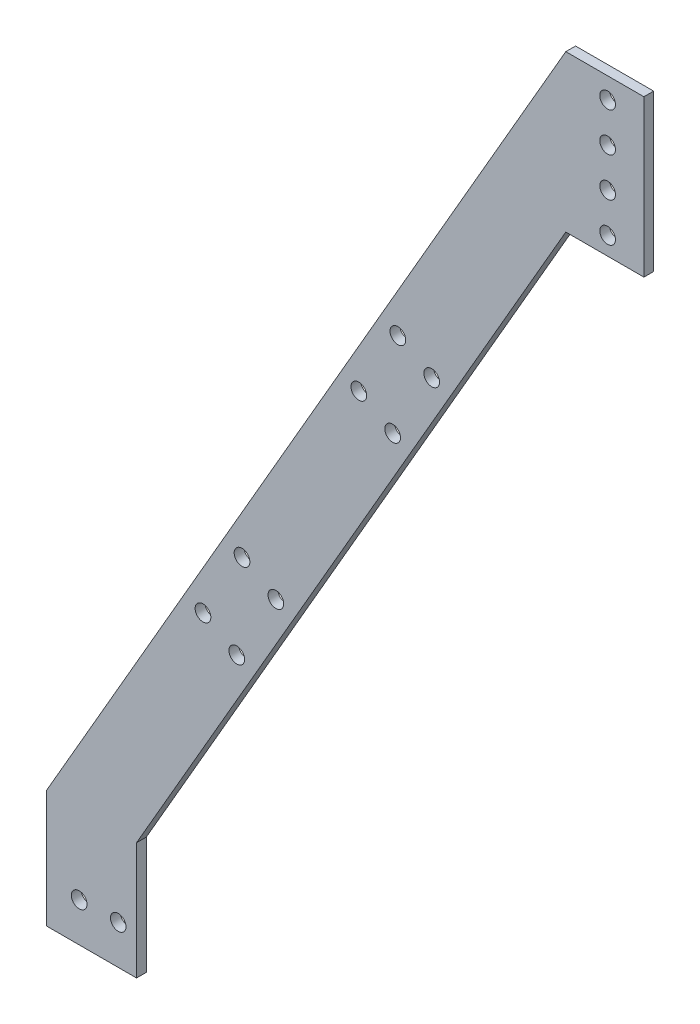
SolidWorks part; units mm, degrees
material "6061-T6 (SS)"
ref_plane "Front Plane" through (0, 0, 0) normal (0, 0, 1) x (1, 0, 0)
ref_plane "Top Plane" through (0, 0, 0) normal (0, 1, 0) x (1, 0, 0)
ref_plane "Right Plane" through (0, 0, 0) normal (1, 0, 0) x (0, 0, -1)
sketch "Sketch1" plane through (0, 0, 0) normal (0, 0, 1) x (1, 0, 0)
  line L0 (0, 0) -> (0, 38.1)
  line L1 (0, 38.1) -> (168.91, 330.6607)
  line L2 (168.91, 330.6607) -> (194.31, 330.6607)
  line L3 (194.31, 330.6607) -> (194.31, 279.8607)
  line L4 (194.31, 279.8607) -> (168.91, 279.8607)
  line L5 (168.91, 279.8607) -> (29.3294, 38.1)
  line L6 (29.3294, 38.1) -> (29.3294, 0)
  line L7 (29.3294, 0) -> (0, 0)
  dimension "D1" = 25.4
  dimension "D2" = 150
  dimension "D3" = 25.4
  dimension "D4" = 25.4
  dimension "D5" = 38.1
  dimension "D6" = 38.1
  dimension "D7" = 337.82
extrude "Boss-Extrude1" add sketch "Sketch1" along normal blind 3.175
sketch "Sketch2" plane through (0, 0, 3.175) normal (0, 0, 1) x (1, 0, 0)
  line L0 (194.31, 279.8607) -> (194.31, 330.6607) construction
  line L3 (194.31, 330.6607) -> (168.91, 330.6607) construction
  line L11 (0, 0) -> (29.3294, 0) construction
  line L13 (0, 38.1) -> (0, 0) construction
  circle A0 centre (182.5111, 323.85) radius 2.5527
  circle A1 centre (182.5111, 311.15) radius 2.5527
  circle A3 centre (23.3801, 12.7) radius 2.5224
  circle A4 centre (10.6801, 12.7) radius 2.5527
  circle A6 centre (182.5111, 285.75) radius 2.5527
  circle A10 centre (182.5111, 298.45) radius 2.5527
  dimension "D1" = 5.1054
  dimension "D2" = 5.1054
  dimension "D3" = 11.7989
  dimension "D4" = 6.8107
  dimension "D5" = 11.7989
  dimension "D6" = 12.7
  dimension "D7" = 10.6801
  dimension "D8" = 12.7
  dimension "D9" = 12.7
  dimension "D10" = 12.7
  dimension "D11" = 5.1054
  dimension "D12" = 12.7
  dimension "D13" = 11.7989
  dimension "D14" = 11.7989
  dimension "D15" = 5.1054
  dimension "D16" = 12.7
extrude "Cut-Extrude1" cut sketch "Sketch2" against normal through all
sketch "Sketch3" plane through (0, 0, 3.175) normal (0, 0, 1) x (1, 0, 0)
  line L0 (168.91, 279.8607) -> (146.913, 292.5607) construction
  line L1 (168.91, 330.6607) -> (0, 38.1) construction
  line L2 (29.3294, 38.1) -> (168.91, 279.8607) construction
  line L3 (29.3294, 38.1) -> (7.3323, 50.8) construction
  circle A0 centre (101.6122, 201.3975) radius 2.5527
  circle A1 centre (125.3107, 217.0446) radius 2.5527
  circle A2 centre (114.3122, 223.3946) radius 2.5527
  circle A3 centre (112.6107, 195.0475) radius 2.5527
  circle A4 centre (50.9316, 113.6161) radius 2.5527
  circle A5 centre (63.6316, 135.6132) radius 2.5527
  circle A6 centre (74.6301, 129.2632) radius 2.5527
  circle A7 centre (61.9301, 107.2661) radius 2.5527
  dimension "D2" = 5.1054
  dimension "D3" = 5.1054
  dimension "D4" = 5.1054
  dimension "D5" = 5.1054
  dimension "D6" = 101.6
  dimension "D8" = 76.2
  dimension "D9" = 101.6
  dimension "D10" = 6.35
  dimension "D11" = 6.35
  dimension "D12" = 6.35
  dimension "D13" = 6.35
  dimension "D15" = 76.2
  dimension "D16" = 101.6
  dimension "D17" = 101.6
  dimension "D18" = 76.2
  dimension "D19" = 5.1054
  dimension "D20" = 5.1054
  dimension "D21" = 5.1054
  dimension "D22" = 5.1054
  dimension "D23" = 6.35
  dimension "D24" = 6.35
  dimension "D25" = 6.35
  dimension "D26" = 6.35
  dimension "D1" = 90
  dimension "D7" = 76.2
  dimension "D14" = 90
extrude "Cut-Extrude2" cut sketch "Sketch3" against normal through all
